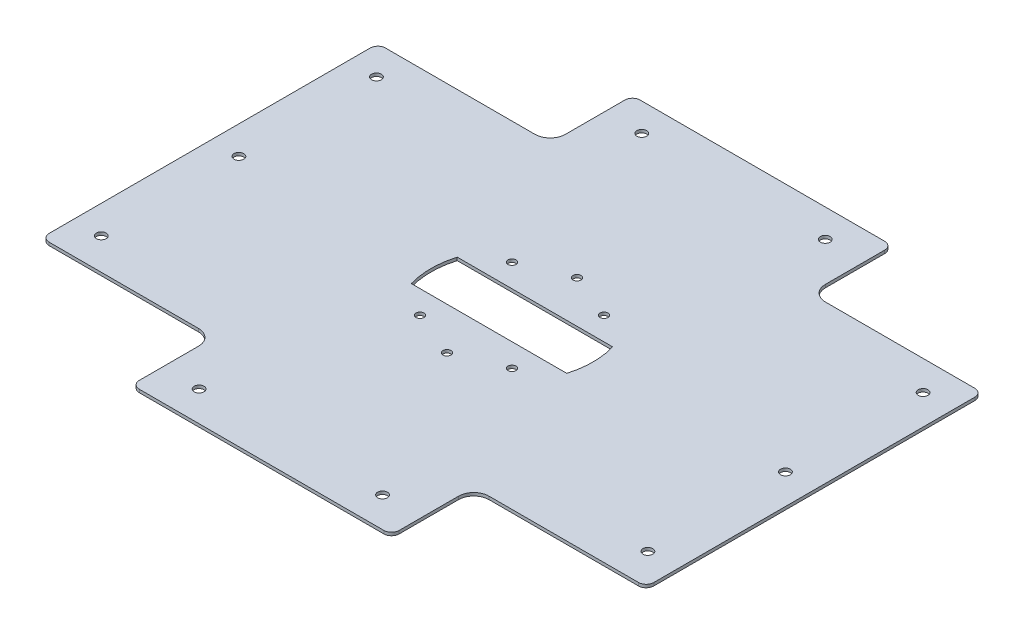
SolidWorks part; units mm, degrees
material "7075-T6, Пластина (SS)"
ref_plane "Спереди" through (0, 0, 0) normal (0, 0, 1) x (1, 0, 0)
ref_plane "Сверху" through (0, 0, 0) normal (0, 1, 0) x (1, 0, 0)
ref_plane "Справа" through (0, 0, 0) normal (1, 0, 0) x (0, 0, -1)
sketch "Эскиз1" plane through (0, 0, 0) normal (0, 1, 0) x (1, 0, 0)
  line L1 (-80, -163.8055) -> (80, -163.8055)
  line L2 (-197.7687, -105) -> (-197.7687, 105)
  line L3 (-80, 163.8055) -> (80, 163.8055)
  line L4 (197.7687, -105) -> (197.7687, 105)
  line L5 (-236.4266, 144.4996) -> (-147.9018, 144.4996) construction
  line L6 (-147.9018, 144.4996) -> (286.4952, 144.4996) construction
  line L18 (-284.5497, 0) -> (284.3305, 0) construction
  line L19 (-160.9018, 110) -> (-134.9018, 110)
  line L20 (-160.9018, 110) -> (-160.9018, 0)
  line L21 (-160.9018, 0) -> (-134.9018, 0)
  line L22 (-134.9018, 110) -> (-134.9018, 0)
  line L23 (-147.9018, -182.6295) -> (-147.9018, 219.9923) construction
  line L24 (-160.9018, 0) -> (-134.9018, 0)
  line L25 (-160.9018, 0) -> (-160.9018, -110)
  line L26 (-160.9018, -110) -> (-134.9018, -110)
  line L27 (-134.9018, 0) -> (-134.9018, -110)
  line L28 (-97.9018, -119.4996) -> (-197.9018, -119.4996)
  line L29 (-97.9018, 169.4996) -> (-197.9018, 169.4996)
  line L30 (-97.9018, 169.4996) -> (-97.9018, 119.4996)
  line L31 (-97.9018, 119.4996) -> (-197.9018, 119.4996)
  line L32 (-197.9018, 169.4996) -> (-197.9018, 119.4996)
  line L33 (-97.9018, 169.4996) -> (-197.9018, 119.4996) construction
  line L34 (-97.9018, 119.4996) -> (-197.9018, 169.4996) construction
  line L35 (-197.9018, -169.4996) -> (-197.9018, -119.4996)
  line L36 (-97.9018, -169.4996) -> (-197.9018, -169.4996)
  line L37 (-97.9018, -169.4996) -> (-97.9018, -119.4996)
  line L39 (-85, 120) -> (-85, 158.8055)
  line L40 (0, 262.7398) -> (0, -186.5795) construction
  line L41 (-192.7687, 110) -> (-95, 110)
  line L43 (-192.7687, -110) -> (-95, -110)
  line L44 (-85, -120) -> (-85, -158.8055)
  line L45 (85, 120) -> (85, 158.8055)
  line L46 (192.7687, 110) -> (95, 110)
  line L47 (192.7687, -110) -> (95, -110)
  line L48 (85, -120) -> (85, -158.8055)
  line L49 (97.9018, -169.4996) -> (97.9018, -119.4996)
  line L50 (97.9018, -169.4996) -> (197.9018, -169.4996)
  line L51 (197.9018, -169.4996) -> (197.9018, -119.4996)
  line L52 (97.9018, -119.4996) -> (197.9018, -119.4996)
  line L53 (160.9018, 0) -> (160.9018, -110)
  line L54 (160.9018, -110) -> (134.9018, -110)
  line L55 (134.9018, 0) -> (134.9018, -110)
  line L56 (160.9018, 0) -> (134.9018, 0)
  line L57 (160.9018, 110) -> (160.9018, 0)
  line L58 (160.9018, 0) -> (134.9018, 0)
  line L59 (134.9018, 110) -> (134.9018, 0)
  line L60 (160.9018, 110) -> (134.9018, 110)
  line L61 (97.9018, 119.4996) -> (197.9018, 119.4996)
  line L62 (197.9018, 169.4996) -> (197.9018, 119.4996)
  line L63 (97.9018, 169.4996) -> (197.9018, 169.4996)
  line L64 (97.9018, 169.4996) -> (97.9018, 119.4996)
  arc A0 (85, -120) -> (95, -110) centre (95, -120) cw
  arc A1 (85, 120) -> (95, 110) centre (95, 120) ccw
  arc A2 (-95, -110) -> (-85, -120) centre (-95, -120) cw
  arc A3 (-85, 120) -> (-95, 110) centre (-95, 120) cw
  arc A4 (192.7687, -110) -> (197.7687, -105) centre (192.7687, -105) ccw
  arc A5 (85, -158.8055) -> (80, -163.8055) centre (80, -158.8055) cw
  arc A6 (-85, -158.8055) -> (-80, -163.8055) centre (-80, -158.8055) ccw
  arc A7 (-192.7687, -110) -> (-197.7687, -105) centre (-192.7687, -105) cw
  arc A8 (-192.7687, 110) -> (-197.7687, 105) centre (-192.7687, 105) ccw
  arc A9 (197.7687, 105) -> (192.7687, 110) centre (192.7687, 105) ccw
  arc A10 (85, 158.8055) -> (80, 163.8055) centre (80, 158.8055) ccw
  arc A11 (-85, 158.8055) -> (-80, 163.8055) centre (-80, 158.8055) cw
  circle A12 centre (59.4553, 145.4623) radius 3.2
  circle A13 centre (59.4553, -144.1486) radius 3.2
  circle A14 centre (-60.5447, -144.1486) radius 3.2
  circle A15 centre (-60.5447, 145.4623) radius 3.2
  circle A16 centre (-179.3134, 90.6569) radius 3.2
  circle A17 centre (-179.3134, -89.3431) radius 3.2
  circle A18 centre (-179.3134, 0.6569) radius 3.2
  circle A19 centre (178.224, 90.6569) radius 3.2
  circle A20 centre (178.224, 0.6569) radius 3.2
  circle A21 centre (178.224, -89.3431) radius 3.2
  point P0 (0, 0)
  point P3 (85, -110)
  point P17 (-147.9018, 110)
  point P18 (-147.9018, 110)
  point P20 (-147.9018, 0)
  point P21 (0, 0)
  point P22 (-150, 134)
  point P37 (-147.9018, 144.4996)
  point P46 (85, 110)
  point P52 (-85, -110)
  point P55 (-85, 110)
  point P56 (-147.9018, 0)
  point P77 (197.7687, -110)
  point P80 (85, -163.8055)
  point P83 (-85, -163.8055)
  point P86 (-197.7687, -110)
  point P89 (-197.7687, 110)
  point P92 (197.7687, 110)
  point P95 (85, 163.8055)
  point P98 (-85, 163.8055)
  dimension "D2" = 50
  dimension "D6" = 10
  dimension "D4" = 5
  dimension "D3" = 26
  dimension "D5" = 338.9991
  dimension "D7" = 395.5373
  dimension "D8" = 110
  dimension "D9" = 170
  dimension "D10" = 100
  dimension "D13" = 9.4996
  dimension "D14" = 12.9018
sketch "Эскиз2" plane through (0, 0, 0) normal (0, 1, 0) x (1, 0, 0)
  line L0 (-162.9105, 114) -> (-136.9105, 114)
  line L1 (-162.9105, 114) -> (-162.9105, 0)
  line L2 (-162.9105, 0) -> (-136.9105, 0)
  line L3 (-136.9105, 114) -> (-136.9105, 0)
  line L4 (-149.9105, -192.6295) -> (-149.9105, 209.9923) construction
  line L5 (-162.9105, 0) -> (-136.9105, 0)
  line L6 (-162.9105, 0) -> (-162.9105, -114)
  line L7 (-162.9105, -114) -> (-136.9105, -114)
  line L8 (-136.9105, 0) -> (-136.9105, -114)
  line L9 (-99.9105, -123.5568) -> (-199.9105, -123.5568)
  line L10 (-99.9105, 163.4996) -> (-199.9105, 163.4996)
  line L11 (-99.9105, 163.4996) -> (-99.9105, 123.4996)
  line L12 (-99.9105, 123.4996) -> (-199.9105, 123.4996)
  line L13 (-199.9105, 163.4996) -> (-199.9105, 123.4996)
  line L14 (-199.9105, -163.5568) -> (-199.9105, -123.5568)
  line L15 (-99.9105, -163.5568) -> (-199.9105, -163.5568)
  line L16 (-99.9105, -163.5568) -> (-99.9105, -123.5568)
  line L17 (-284.5497, 0) -> (284.3305, 0) construction
  point P11 (-149.9105, 0)
  point P12 (-149.9105, 0)
sketch "Эскиз3" plane through (0, 0, 0) normal (0, 1, 0) x (1, 0, 0)
  line L0 (-89.8176, -177.9027) -> (70.2405, -177.9027)
  line L1 (-209.7886, -106.9112) -> (-209.7886, 106.8353)
  line L2 (-80.029, 172.0973) -> (50.2405, 172.0973)
  line L3 (170.2114, -106.9112) -> (170.2114, 103.9123)
  line L4 (-87.1938, 124.0033) -> (-87.1938, 164.9326)
  line L5 (-202.6239, 114) -> (-97.1971, 114)
  line L6 (-202.6239, -114.076) -> (-106.9857, -114.076)
  line L7 (-96.9823, -124.0793) -> (-96.9823, -170.738)
  line L8 (57.4052, 121.0803) -> (57.4052, 164.9326)
  line L9 (163.0467, 111.077) -> (67.4085, 111.077)
  line L10 (163.0467, -114.076) -> (87.4085, -114.076)
  line L11 (77.4052, -124.0793) -> (77.4052, -170.738)
  line L13 (-162.9105, 114) -> (-136.9105, 114) construction
  arc A0 (77.4052, -124.0793) -> (87.4085, -114.076) centre (87.4085, -124.0793) cw
  arc A1 (57.4052, 121.0803) -> (67.4085, 111.077) centre (67.4085, 121.0803) ccw
  arc A2 (-106.9857, -114.076) -> (-96.9823, -124.0793) centre (-106.9857, -124.0793) cw
  arc A3 (-87.1938, 124.0033) -> (-97.1971, 114) centre (-97.1971, 124.0033) cw
  arc A4 (-80.029, 172.0973) -> (-87.1938, 164.9326) centre (-80.029, 164.9326) ccw
  arc A5 (50.2405, 172.0973) -> (57.4052, 164.9326) centre (50.2405, 164.9326) cw
  arc A6 (170.2114, 103.9123) -> (163.0467, 111.077) centre (163.0467, 103.9123) ccw
  arc A7 (170.2114, -106.9112) -> (163.0467, -114.076) centre (163.0467, -106.9112) cw
  arc A8 (70.2405, -177.9027) -> (77.4052, -170.738) centre (70.2405, -170.738) ccw
  arc A9 (-89.8176, -177.9027) -> (-96.9823, -170.738) centre (-89.8176, -170.738) cw
  arc A10 (-209.7886, -106.9112) -> (-202.6239, -114.076) centre (-202.6239, -106.9112) ccw
  arc A11 (-209.7886, 106.8353) -> (-202.6239, 114) centre (-202.6239, 106.8353) cw
  point P36 (115.2276, 111.077)
  point P39 (-149.9105, 114)
  point P42 (-149.9105, 114)
  dimension "D3" = 10.0033
  dimension "D4" = 7.1647
  dimension "D1" = 380
  dimension "D2" = 350
  dimension "D5" = 112.8062
  dimension "D6" = 63.8267
  dimension "D7" = 61.0203
extrude "Бобышка-Вытянуть1" add sketch "Эскиз1" along normal blind 2 separate body contours A11 L39 A3 L41 L22 L27 L43 A2 L44 A6 L1 A5 L48 A0 L47 L55 L59 L46 A1 L45 A10 L3 | L4 A9 L46 L57 L53 L47 A4 | L46 L59 L56 L57 | L53 L56 L55 L47 | L27 L21 L25 L26 | L41 A8 L2 A7 L43 L25 L20 | L22 L19 L20 L21 region at (0.0009, 0, 0.0011) region at (-147.9018, 0, 55) region at (147.9018, 0, 55) region at (-176.8353, 0, 107.7693) region at (-147.9018, 0, -55) region at (163.1325, 0, 55) region at (147.9018, 0, -55)
sketch "Эскиз4" plane through (0, 2, 0) normal (0, 1, 0) x (1, 0, 0)
  line L0 (197.7687, 0) -> (-197.7687, 0) construction
  line L1 (197.7687, -105) -> (197.7687, 105) construction
  line L2 (-197.7687, -105) -> (-197.7687, 105) construction
  line L3 (197.7687, 0) -> (10, 0) construction
  line L4 (-22, 0) -> (0, 0) construction
  line L5 (0, 0) -> (0, 42.54) construction
  circle A1 centre (0, 42.54) radius 2.6
  circle A2 centre (0, -42.54) radius 2.6
  circle A7 centre (0, 0) radius 42.54 construction
  circle A8 centre (30.0803, 30.0803) radius 2.6
  circle A9 centre (-30.0803, -30.0803) radius 2.6
  circle A10 centre (-30.0803, 30.0803) radius 2.6
  circle A11 centre (30.0803, -30.0803) radius 2.6
  point P14 (0, 0)
  point P21 (0, 0)
  point P26 (0, 0)
  point P29 (0, 0)
  dimension "D1" = 2
  dimension "D2" = 5.2
  dimension "D3" = 2
  dimension "D4" = 2
extrude "Вырез-Вытянуть1" cut sketch "Эскиз4" against normal through all
sketch "Эскиз5" plane through (0, 0, 0) normal (0, -1, 0) x (1, 0, 0)
  line L0 (50.8331, -15) -> (-50.8331, -15)
  line L7 (50.8331, 15) -> (-50.8331, 15)
  arc A0 (50.8331, -15) -> (50.8331, 15) centre (0, 0) ccw
  arc A1 (-50.8331, 15) -> (-50.8331, -15) centre (0, 0) ccw
  point P0 (0, 0)
  dimension "D2" = 101.6661
  dimension "D3" = 101.6661
  dimension "D1" = 30
extrude "Вырез-Вытянуть2" cut sketch "Эскиз5" against normal through all
